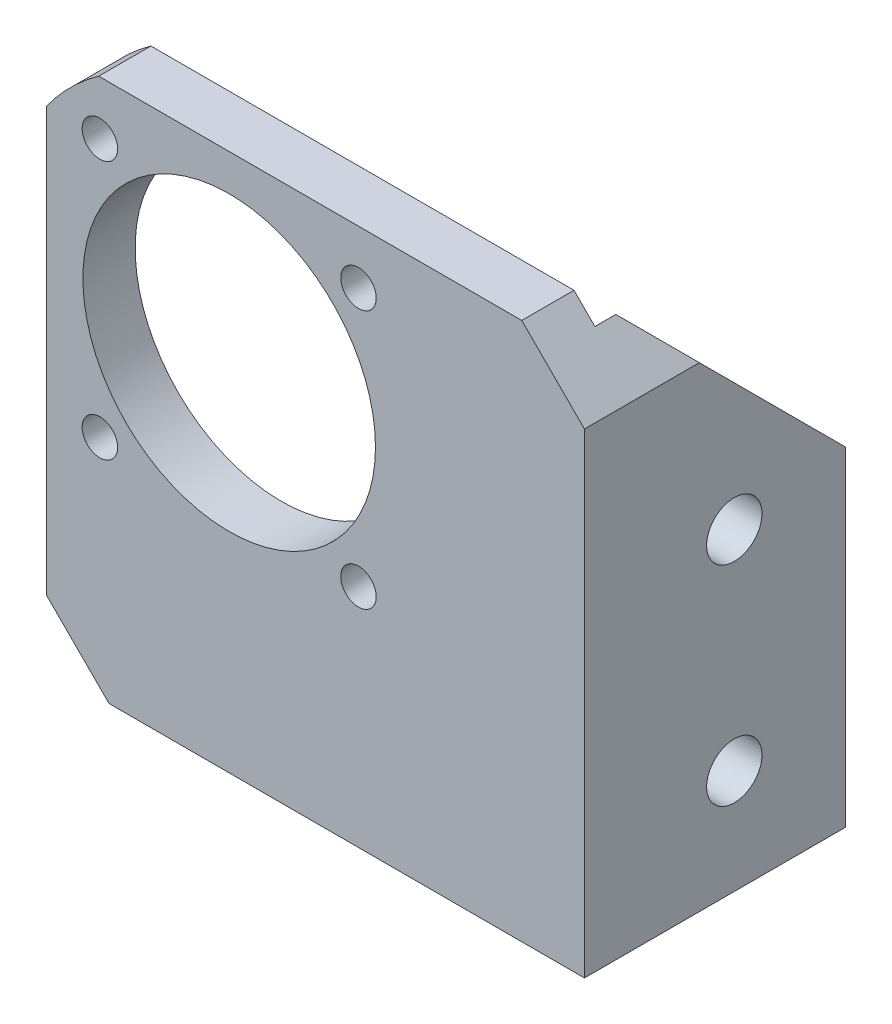
SolidWorks part; units mm, degrees
ref_plane "Plan de face" through (0, 0, 0) normal (0, 0, 1) x (1, 0, 0)
ref_plane "Plan de dessus" through (0, 0, 0) normal (0, 1, 0) x (1, 0, 0)
ref_plane "Plan de droite" through (0, 0, 0) normal (1, 0, 0) x (0, 0, -1)
sketch "Esquisse2" plane through (0, 0, 0) normal (0, 0, 1) x (1, 0, 0)
  line L4 (12.49, 17.5) -> (-12.49, 17.5)
  line L5 (-17.5, 12.49) -> (-17.5, -12.49)
  line L6 (-12.49, -17.5) -> (12.49, -17.5)
  line L7 (17.5, -12.49) -> (17.5, 12.49)
  line L8 (12.49, 17.5) -> (-12.49, 17.5)
  line L9 (-17.5, 12.49) -> (-17.5, -12.49)
  line L10 (-12.49, -17.5) -> (12.49, -17.5)
  line L11 (17.5, -12.49) -> (17.5, 12.49)
  circle A0 centre (0, 0) radius 14 construction
  circle A1 centre (0, 0) radius 14
  circle A2 centre (-12.3744, -12.3744) radius 1.7 construction
  circle A3 centre (12.3744, -12.3744) radius 1.7 construction
  arc A4 (17.5, 12.49) -> (12.49, 17.5) centre (0, 0) ccw
  arc A5 (-12.49, 17.5) -> (-17.5, 12.49) centre (0, 0) ccw
  arc A6 (-17.5, -12.49) -> (-12.49, -17.5) centre (0, 0) ccw
  arc A7 (12.49, -17.5) -> (17.5, -12.49) centre (0, 0) ccw
  arc A8 (17.5, 12.49) -> (12.49, 17.5) centre (0, 0) ccw
  arc A9 (-12.49, 17.5) -> (-17.5, 12.49) centre (0, 0) ccw
  arc A10 (-17.5, -12.49) -> (-12.49, -17.5) centre (0, 0) ccw
  arc A11 (12.49, -17.5) -> (17.5, -12.49) centre (0, 0) ccw
  circle A12 centre (12.3744, 12.3744) radius 1.7 construction
  circle A13 centre (-12.3744, 12.3744) radius 1.7 construction
  circle A14 centre (-12.3744, -12.3744) radius 1.7
  circle A15 centre (12.3744, -12.3744) radius 1.7
  circle A16 centre (12.3744, 12.3744) radius 1.7
  circle A17 centre (-12.3744, 12.3744) radius 1.7
  dimension "D1" = 0
extrude "Boss.-Extru.1" add sketch "Esquisse2" along normal blind 5
sketch "Esquisse3" plane through (0, 0, 5) normal (0, 0, 1) x (1, 0, 0)
  line L0 (-17.5, -12.49) -> (-17.5, -34)
  line L1 (46, -34) -> (-59, -34) construction
  line L2 (12.49, 17.5) -> (34, 17.5)
  line L3 (34, 416.3) -> (34, -34) construction
  line L4 (-17.5, -34) -> (34, -34)
  line L5 (34, -34) -> (34, 17.5)
  line L6 (-12.49, -17.5) -> (12.49, -17.5) construction
  line L7 (17.5, -12.49) -> (17.5, 12.49) construction
  line L8 (-12.49, -17.5) -> (12.49, -17.5)
  line L9 (17.5, -12.49) -> (17.5, 12.49)
  arc A0 (-17.5, -12.49) -> (-12.49, -17.5) centre (0, 0) ccw construction
  arc A1 (12.49, -17.5) -> (17.5, -12.49) centre (0, 0) ccw construction
  arc A2 (17.5, 12.49) -> (12.49, 17.5) centre (0, 0) ccw construction
  arc A3 (-17.5, -12.49) -> (-12.49, -17.5) centre (0, 0) ccw
  arc A4 (12.49, -17.5) -> (17.5, -12.49) centre (0, 0) ccw
  arc A5 (17.5, 12.49) -> (12.49, 17.5) centre (0, 0) ccw
extrude "Boss.-Extru.2" add sketch "Esquisse3" against normal blind 5 separate body
sketch "Esquisse4" plane through (0, 0, 0) normal (0, 0, -1) x (-1, 0, 0)
  line L0 (-34, 17.5) -> (-34, -34)
  line L1 (-34, -34) -> (17.65, -34)
  line L2 (17.65, -34) -> (17.5, -30)
  line L3 (17.5, -12.49) -> (17.5, -34) construction
  line L4 (17.5, -30) -> (-30, -30)
  line L5 (-30, -30) -> (-30, 17.5)
  line L6 (-30, 17.5) -> (-34, 17.5)
  dimension "D1" = 4
  dimension "D2" = 4
extrude "Boss.-Extru.3" add sketch "Esquisse4" along normal blind 20
chamfer "Chanfrein1" distance 20 angle 45 2 edges at (32, 17.5, -20) (-17.575, -32, -20)
sketch "Esquisse5" plane through (0, 0, 0) normal (0, 0, 1) x (1, 0, 0)
  line L3 (-17.5, -34) -> (-17.5, -30)
  line L4 (-17.5, -30) -> (-17.65, -34)
  line L5 (-17.65, -34) -> (-17.5, -34)
  line L6 (-17.5, -34) -> (-17.5, -30)
  line L8 (-17.65, -34) -> (-17.5, -34)
  line L9 (-17.5, -30) -> (-17.65, -34)
  dimension "D1" = 0
extrude "Enlèv. mat.-Extru.1" cut sketch "Esquisse5" against normal blind 25
chamfer "Chanfrein2" distance 6 angle 45 2 edges at (-17.5, -34, 2.4251) (34, 17.5, 2.5)
sketch "Esquisse6" plane through (30, 0, 0) normal (-1, 0, 0) x (0, 0, 1)
  circle A0 centre (-9.34, -4) radius 2.65 construction
  circle A1 centre (-9.34, -4) radius 2.65
  circle A2 centre (-9.34, -24) radius 2.65 construction
  circle A3 centre (-9.34, -24) radius 2.65
extrude "Enlèv. mat.-Extru.2" cut sketch "Esquisse6" against normal blind 25
sketch "Esquisse7" plane through (0, -30, 0) normal (0, 1, 0) x (1, 0, 0)
  circle A0 centre (1, 9.34) radius 2.65 construction
  circle A1 centre (1, 9.34) radius 2.65
  circle A2 centre (21, 9.34) radius 2.65 construction
  circle A3 centre (21, 9.34) radius 2.65
extrude "Enlèv. mat.-Extru.3" cut sketch "Esquisse7" against normal blind 25
